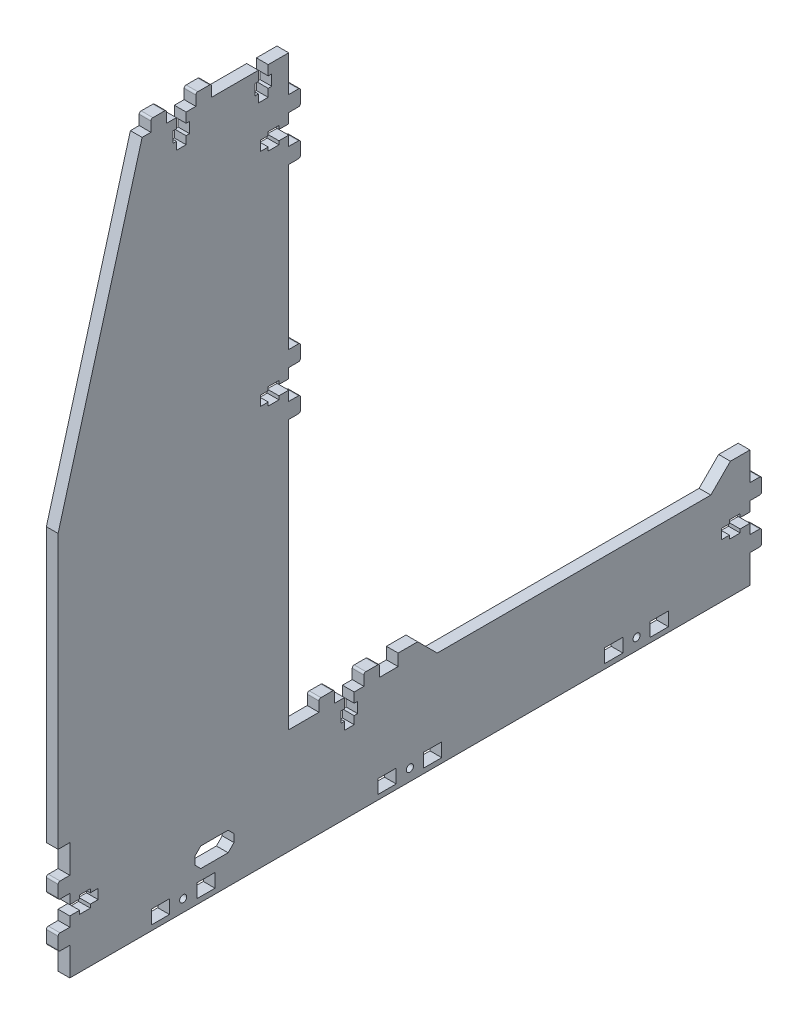
SolidWorks part; units mm, degrees
ref_plane "Plan de face" through (0, 0, 0) normal (0, 0, 1) x (1, 0, 0)
ref_plane "Plan de dessus" through (0, 0, 0) normal (0, 1, 0) x (1, 0, 0)
ref_plane "Plan de droite" through (0, 0, 0) normal (1, 0, 0) x (0, 0, -1)
sketch "Esquisse2" plane through (0, 0, 0) normal (1, 0, 0) x (0, 0, -1)
  line L0 (-180, 200) -> (-180, 60)
  line L1 (-180, 200) -> (-137, 354)
  line L2 (-137, 354) -> (-62, 354)
  line L3 (-62, 354) -> (-62, 54)
  line L4 (-62, 54) -> (-6, 54)
  line L5 (-6, 54) -> (-6, 60)
  line L6 (-6, 60) -> (4, 60)
  line L7 (4, 60) -> (14, 50)
  line L8 (14, 50) -> (154, 50)
  line L9 (154, 50) -> (164, 60)
  line L10 (164, 60) -> (174, 60)
  line L11 (174, 60) -> (174, 0)
  line L12 (174, 0) -> (-174, 0)
  line L13 (4, 60) -> (119.7586, 60) construction
  line L14 (-180, 60) -> (-174, 60)
  line L15 (-62, 204) -> (0, 204) construction
  line L16 (-174, 60) -> (-174, 0)
  line L17 (0, 0) -> (0, 204) construction
  line L18 (-174, 6) -> (174, 6) construction
  point P2 (0, 0)
  point P18 (-62, 204)
  line B0 (-132.3, 9.6336) -> (-123, 9.6336)
  line B1 (-132.3, 9.6336) -> (-132.3, 2.6336)
  line B2 (-132.3, 2.6336) -> (-123, 2.6336)
  line B3 (-123, 9.6336) -> (-123, 2.6336)
  line B4 (-109, 9.6336) -> (-109, 2.6336)
  line B5 (-99.7, 2.6336) -> (-109, 2.6336)
  line B6 (-99.7, 9.6336) -> (-99.7, 2.6336)
  line B7 (-99.7, 9.6336) -> (-109, 9.6336)
  circle B8 centre (-116, 6.1336) radius 1.8
  line B9 (-16.3, 9.5) -> (-7, 9.5)
  line B10 (-16.3, 9.5) -> (-16.3, 2.5)
  line B11 (-16.3, 2.5) -> (-7, 2.5)
  line B12 (-7, 9.5) -> (-7, 2.5)
  line B13 (7, 9.5) -> (7, 2.5)
  line B14 (16.3, 2.5) -> (7, 2.5)
  line B15 (16.3, 9.5) -> (16.3, 2.5)
  line B16 (16.3, 9.5) -> (7, 9.5)
  circle B17 centre (0, 6) radius 1.8
  line B18 (99.7, 9.5) -> (109, 9.5)
  line B19 (99.7, 9.5) -> (99.7, 2.5)
  line B20 (99.7, 2.5) -> (109, 2.5)
  line B21 (109, 9.5) -> (109, 2.5)
  line B22 (123, 9.5) -> (123, 2.5)
  line B23 (132.3, 2.5) -> (123, 2.5)
  line B24 (132.3, 9.5) -> (132.3, 2.5)
  line B25 (132.3, 9.5) -> (123, 9.5)
  circle B26 centre (116, 6) radius 1.8
  dimension "D1" = 348
  dimension "D2" = 354
  dimension "D3" = 75
  dimension "D4" = 62
  dimension "D5" = 56
  dimension "D6" = 6
  dimension "D7" = 10
  dimension "D8" = 10
  dimension "D9" = 118
  dimension "D10" = 45
  dimension "D11" = 10
  dimension "D12" = 60
  dimension "D14" = 6
  dimension "D15" = 58
  dimension "s" = 200
  dimension "D16" = 58
sketch_block_instance "attache_femelle-1"
sketch_block "attache_femelle" parameters "D1"=3.6, "D2"=9.3, "D3"=7, "D4"=7
sketch_block_instance "attache_femelle-2"
sketch_block_instance "attache_femelle-5"
extrude "Boss.-Extru.1" add sketch "Esquisse2" along normal mid plane 6
sketch "Esquisse4" plane through (3, 0, 0) normal (1, 0, 0) x (0, 0, -1)
  line L0 (174, 30) -> (-174, 30) construction
  line L1 (-62, 54) -> (-62, 360) construction
  line L2 (-6, 54) -> (-56, 54) construction
  line L3 (-174, 0) -> (174, 0) construction
  line L8 (174, 0) -> (174, 60) construction
  line L10 (-62, 54) -> (-62, 354) construction
  line L11 (-6, 54) -> (-62, 54) construction
  line L12 (-174, 60) -> (-174, 0) construction
  line L13 (-62, 354) -> (-137, 354) construction
  line B0 (-174, 14.5) -> (-179, 14.5)
  line B1 (-180, 15.5) -> (-180, 21.5)
  line B2 (-179, 22.5) -> (-174, 22.5)
  line B3 (-174, 22.5) -> (-174, 27.5)
  line B4 (-174, 27.5) -> (-169, 27.5)
  line B5 (-169, 27.5) -> (-169, 25.7)
  line B6 (-169, 25.7) -> (-163.5, 25.7)
  line B7 (-163.5, 25.7) -> (-163.5, 27.5)
  line B8 (-163.5, 27.5) -> (-159.5, 27.5)
  line B9 (-159.5, 27.5) -> (-159.5, 32.5)
  line B10 (-159.5, 30) -> (-174, 30) construction
  line B11 (-174, 45.5) -> (-174, 37.5)
  line B12 (-174, 22.5) -> (-174, 14.5)
  line B13 (-163.5, 32.5) -> (-159.5, 32.5)
  line B14 (-163.5, 34.3) -> (-163.5, 32.5)
  line B15 (-169, 34.3) -> (-163.5, 34.3)
  line B16 (-169, 32.5) -> (-169, 34.3)
  line B17 (-174, 32.5) -> (-169, 32.5)
  line B18 (-174, 37.5) -> (-174, 32.5)
  line B19 (-179, 37.5) -> (-174, 37.5)
  line B20 (-180, 44.5) -> (-180, 38.5)
  line B21 (-174, 45.5) -> (-179, 45.5)
  line B22 (-174, 27.5) -> (-174, 32.5)
  arc B23 (-180, 21.5) -> (-179, 22.5) centre (-179, 21.5) cw
  arc B24 (-179, 14.5) -> (-180, 15.5) centre (-179, 15.5) cw
  arc B25 (-179, 45.5) -> (-180, 44.5) centre (-179, 44.5) ccw
  arc B26 (-180, 38.5) -> (-179, 37.5) centre (-179, 38.5) ccw
  line B27 (174, 45.5) -> (179, 45.5)
  line B28 (180, 44.5) -> (180, 38.5)
  line B29 (179, 37.5) -> (174, 37.5)
  line B30 (174, 37.5) -> (174, 32.5)
  line B31 (174, 32.5) -> (169, 32.5)
  line B32 (169, 32.5) -> (169, 34.3)
  line B33 (169, 34.3) -> (163.5, 34.3)
  line B34 (163.5, 34.3) -> (163.5, 32.5)
  line B35 (163.5, 32.5) -> (159.5, 32.5)
  line B36 (159.5, 32.5) -> (159.5, 27.5)
  line B37 (159.5, 30) -> (174, 30) construction
  line B38 (174, 14.5) -> (174, 22.5)
  line B39 (174, 37.5) -> (174, 45.5)
  line B40 (163.5, 27.5) -> (159.5, 27.5)
  line B41 (163.5, 25.7) -> (163.5, 27.5)
  line B42 (169, 25.7) -> (163.5, 25.7)
  line B43 (169, 27.5) -> (169, 25.7)
  line B44 (174, 27.5) -> (169, 27.5)
  line B45 (174, 22.5) -> (174, 27.5)
  line B46 (179, 22.5) -> (174, 22.5)
  line B47 (180, 15.5) -> (180, 21.5)
  line B48 (174, 14.5) -> (179, 14.5)
  line B49 (174, 32.5) -> (174, 27.5)
  arc B50 (180, 38.5) -> (179, 37.5) centre (179, 38.5) cw
  arc B51 (179, 45.5) -> (180, 44.5) centre (179, 44.5) cw
  arc B52 (179, 14.5) -> (180, 15.5) centre (179, 15.5) ccw
  arc B53 (180, 21.5) -> (179, 22.5) centre (179, 21.5) ccw
  line B54 (-46.5, 54) -> (-46.5, 59)
  line B55 (-45.5, 60) -> (-39.5, 60)
  line B56 (-38.5, 59) -> (-38.5, 54)
  line B57 (-38.5, 54) -> (-33.5, 54)
  line B58 (-33.5, 54) -> (-33.5, 49)
  line B59 (-33.5, 49) -> (-35.3, 49)
  line B60 (-35.3, 49) -> (-35.3, 43.5)
  line B61 (-35.3, 43.5) -> (-33.5, 43.5)
  line B62 (-33.5, 43.5) -> (-33.5, 39.5)
  line B63 (-33.5, 39.5) -> (-28.5, 39.5)
  line B64 (-31, 39.5) -> (-31, 54) construction
  line B65 (-15.5, 54) -> (-23.5, 54)
  line B66 (-38.5, 54) -> (-46.5, 54)
  line B67 (-28.5, 43.5) -> (-28.5, 39.5)
  line B68 (-26.7, 43.5) -> (-28.5, 43.5)
  line B69 (-26.7, 49) -> (-26.7, 43.5)
  line B70 (-28.5, 49) -> (-26.7, 49)
  line B71 (-28.5, 54) -> (-28.5, 49)
  line B72 (-23.5, 54) -> (-28.5, 54)
  line B73 (-23.5, 59) -> (-23.5, 54)
  line B74 (-16.5, 60) -> (-22.5, 60)
  line B75 (-15.5, 54) -> (-15.5, 59)
  line B76 (-33.5, 54) -> (-28.5, 54)
  arc B77 (-39.5, 60) -> (-38.5, 59) centre (-39.5, 59) cw
  arc B78 (-46.5, 59) -> (-45.5, 60) centre (-45.5, 59) cw
  arc B79 (-15.5, 59) -> (-16.5, 60) centre (-16.5, 59) ccw
  arc B80 (-22.5, 60) -> (-23.5, 59) centre (-22.5, 59) ccw
  line B81 (-62, 222.5) -> (-57, 222.5)
  line B82 (-56, 221.5) -> (-56, 215.5)
  line B83 (-57, 214.5) -> (-62, 214.5)
  line B84 (-62, 214.5) -> (-62, 209.5)
  line B85 (-62, 209.5) -> (-67, 209.5)
  line B86 (-67, 209.5) -> (-67, 211.3)
  line B87 (-67, 211.3) -> (-72.5, 211.3)
  line B88 (-72.5, 211.3) -> (-72.5, 209.5)
  line B89 (-72.5, 209.5) -> (-76.5, 209.5)
  line B90 (-76.5, 209.5) -> (-76.5, 204.5)
  line B91 (-76.5, 207) -> (-62, 207) construction
  line B92 (-62, 191.5) -> (-62, 199.5)
  line B93 (-62, 214.5) -> (-62, 222.5)
  line B94 (-72.5, 204.5) -> (-76.5, 204.5)
  line B95 (-72.5, 202.7) -> (-72.5, 204.5)
  line B96 (-67, 202.7) -> (-72.5, 202.7)
  line B97 (-67, 204.5) -> (-67, 202.7)
  line B98 (-62, 204.5) -> (-67, 204.5)
  line B99 (-62, 199.5) -> (-62, 204.5)
  line B100 (-57, 199.5) -> (-62, 199.5)
  line B101 (-56, 192.5) -> (-56, 198.5)
  line B102 (-62, 191.5) -> (-57, 191.5)
  line B103 (-62, 209.5) -> (-62, 204.5)
  arc B104 (-56, 215.5) -> (-57, 214.5) centre (-57, 215.5) cw
  arc B105 (-57, 222.5) -> (-56, 221.5) centre (-57, 221.5) cw
  arc B106 (-57, 191.5) -> (-56, 192.5) centre (-57, 192.5) ccw
  arc B107 (-56, 198.5) -> (-57, 199.5) centre (-57, 198.5) ccw
  line B108 (-62, 335.5) -> (-57, 335.5)
  line B109 (-56, 334.5) -> (-56, 328.5)
  line B110 (-57, 327.5) -> (-62, 327.5)
  line B111 (-62, 327.5) -> (-62, 322.5)
  line B112 (-62, 322.5) -> (-67, 322.5)
  line B113 (-67, 322.5) -> (-67, 324.3)
  line B114 (-67, 324.3) -> (-72.5, 324.3)
  line B115 (-72.5, 324.3) -> (-72.5, 322.5)
  line B116 (-72.5, 322.5) -> (-76.5, 322.5)
  line B117 (-76.5, 322.5) -> (-76.5, 317.5)
  line B118 (-76.5, 320) -> (-62, 320) construction
  line B119 (-62, 304.5) -> (-62, 312.5)
  line B120 (-62, 327.5) -> (-62, 335.5)
  line B121 (-72.5, 317.5) -> (-76.5, 317.5)
  line B122 (-72.5, 315.7) -> (-72.5, 317.5)
  line B123 (-67, 315.7) -> (-72.5, 315.7)
  line B124 (-67, 317.5) -> (-67, 315.7)
  line B125 (-62, 317.5) -> (-67, 317.5)
  line B126 (-62, 312.5) -> (-62, 317.5)
  line B127 (-57, 312.5) -> (-62, 312.5)
  line B128 (-56, 305.5) -> (-56, 311.5)
  line B129 (-62, 304.5) -> (-57, 304.5)
  line B130 (-62, 322.5) -> (-62, 317.5)
  arc B131 (-56, 328.5) -> (-57, 327.5) centre (-57, 328.5) cw
  arc B132 (-57, 335.5) -> (-56, 334.5) centre (-57, 334.5) cw
  arc B133 (-57, 304.5) -> (-56, 305.5) centre (-57, 305.5) ccw
  arc B134 (-56, 311.5) -> (-57, 312.5) centre (-57, 311.5) ccw
  line B135 (-90.5, 354) -> (-90.5, 359)
  line B136 (-89.5, 360) -> (-83.5, 360)
  line B137 (-82.5, 359) -> (-82.5, 354)
  line B138 (-82.5, 354) -> (-77.5, 354)
  line B139 (-77.5, 354) -> (-77.5, 349)
  line B140 (-77.5, 349) -> (-79.3, 349)
  line B141 (-79.3, 349) -> (-79.3, 343.5)
  line B142 (-79.3, 343.5) -> (-77.5, 343.5)
  line B143 (-77.5, 343.5) -> (-77.5, 339.5)
  line B144 (-77.5, 339.5) -> (-72.5, 339.5)
  line B145 (-75, 339.5) -> (-75, 354) construction
  line B146 (-59.5, 354) -> (-67.5, 354)
  line B147 (-82.5, 354) -> (-90.5, 354)
  line B148 (-72.5, 343.5) -> (-72.5, 339.5)
  line B149 (-70.7, 343.5) -> (-72.5, 343.5)
  line B150 (-70.7, 349) -> (-70.7, 343.5)
  line B151 (-72.5, 349) -> (-70.7, 349)
  line B152 (-72.5, 354) -> (-72.5, 349)
  line B153 (-67.5, 354) -> (-72.5, 354)
  line B154 (-67.5, 359) -> (-67.5, 354)
  line B155 (-60.5, 360) -> (-66.5, 360)
  line B156 (-59.5, 354) -> (-59.5, 359)
  line B157 (-77.5, 354) -> (-72.5, 354)
  arc B158 (-83.5, 360) -> (-82.5, 359) centre (-83.5, 359) cw
  arc B159 (-90.5, 359) -> (-89.5, 360) centre (-89.5, 359) cw
  arc B160 (-59.5, 359) -> (-60.5, 360) centre (-60.5, 359) ccw
  arc B161 (-66.5, 360) -> (-67.5, 359) centre (-66.5, 359) ccw
  line B162 (-132.5, 354) -> (-132.5, 359)
  line B163 (-131.5, 360) -> (-125.5, 360)
  line B164 (-124.5, 359) -> (-124.5, 354)
  line B165 (-124.5, 354) -> (-119.5, 354)
  line B166 (-119.5, 354) -> (-119.5, 349)
  line B167 (-119.5, 349) -> (-121.3, 349)
  line B168 (-121.3, 349) -> (-121.3, 343.5)
  line B169 (-121.3, 343.5) -> (-119.5, 343.5)
  line B170 (-119.5, 343.5) -> (-119.5, 339.5)
  line B171 (-119.5, 339.5) -> (-114.5, 339.5)
  line B172 (-117, 339.5) -> (-117, 354) construction
  line B173 (-101.5, 354) -> (-109.5, 354)
  line B174 (-124.5, 354) -> (-132.5, 354)
  line B175 (-114.5, 343.5) -> (-114.5, 339.5)
  line B176 (-112.7, 343.5) -> (-114.5, 343.5)
  line B177 (-112.7, 349) -> (-112.7, 343.5)
  line B178 (-114.5, 349) -> (-112.7, 349)
  line B179 (-114.5, 354) -> (-114.5, 349)
  line B180 (-109.5, 354) -> (-114.5, 354)
  line B181 (-109.5, 359) -> (-109.5, 354)
  line B182 (-102.5, 360) -> (-108.5, 360)
  line B183 (-101.5, 354) -> (-101.5, 359)
  line B184 (-119.5, 354) -> (-114.5, 354)
  arc B185 (-125.5, 360) -> (-124.5, 359) centre (-125.5, 359) cw
  arc B186 (-132.5, 359) -> (-131.5, 360) centre (-131.5, 359) cw
  arc B187 (-101.5, 359) -> (-102.5, 360) centre (-102.5, 359) ccw
  arc B188 (-108.5, 360) -> (-109.5, 359) centre (-108.5, 359) ccw
  line B189 (-110, 22) -> (-107, 25)
  line B190 (-107, 15) -> (-93, 15)
  line B191 (-110, 18) -> (-110, 22)
  line B192 (-107, 25) -> (-93, 25)
  line B193 (-90, 18) -> (-90, 22)
  line B194 (-110, 15) -> (-90, 25) construction
  line B195 (-110, 25) -> (-90, 15) construction
  line B196 (-93, 25) -> (-90, 22)
  line B197 (-93, 15) -> (-90, 18)
  line B198 (-110, 18) -> (-107, 15)
  dimension "D1" = 20
  dimension "D2" = 13
  dimension "D3" = 34
  dimension "D4" = 6
  dimension "D5" = 6
  dimension "D6" = 100
  dimension "D7" = 20
sketch_block_instance "attache_male-1"
sketch_block "attache_male" parameters "D7"=1, "D1"=5, "D2"=5, "D3"=5.5, "D4"=1.8, "D5"=4, "D6"=2.5
sketch_block_instance "attache_male-2"
sketch_block_instance "attache_male-3"
sketch_block_instance "attache_male-4"
sketch_block_instance "attache_male-5"
sketch_block_instance "attache_male-6"
sketch_block_instance "attache_male-7"
sketch_block_instance "cable_hole-1"
sketch_block "cable_hole" parameters "D1"=20, "D2"=10
extrude "Boss.-Extru.2" add sketch "Esquisse4" against normal blind 6 contours B186 B162 B164 B185 B163 | B182 B188 B181 B183 B187 | B132 B108 B110 B131 B109 | B128 B134 B127 B129 B133 | B105 B81 B83 B104 B82 | B101 B107 B100 B102 B106 | B20 B26 B19 B21 B25 | B24 B0 B2 B23 B1 | B78 B54 B56 B77 B55 | B74 B80 B73 B75 B79 | B51 B27 B29 B50 B28 | B47 B53 B46 B48 B52 region at (3, 41.5, 176.9749) region at (3, 18.5, 176.9749) region at (3, 18.5, -176.9749) region at (3, 41.5, -176.9749) region at (3, 56.9749, 19.5) region at (3, 56.9749, 42.5) region at (3, 195.5, 59.0251) region at (3, 218.5, 59.0251) region at (3, 308.5, 59.0251) region at (3, 331.5, 59.0251) region at (3, 356.9749, 105.5) region at (3, 356.9749, 128.5)
extrude "Enlèv. mat.-Extru.1" cut sketch "Esquisse4<3>" against normal blind 6 contours B179 B166 B167 B168 B169 B170 B171 B175 B176 B177 B178 | B152 B139 B140 B141 B142 B143 B144 B148 B149 B150 B151 | B125 B112 B113 B114 B115 B116 B117 B121 B122 B123 B124 | B98 B85 B86 B87 B88 B89 B90 B94 B95 B96 B97 | B71 B58 B59 B60 B61 B62 B63 B67 B68 B69 B70 | B22 B4 B5 B6 B7 B8 B9 | B9 B13 B14 B15 B16 B17 | B36 B49 B31 B32 B33 B34 B35 | B36 B40 B41 B42 B43 B44 | B191 B198 B190 B197 B193 B196 B192 B189 region at (3, 30, 166.6427) region at (3, 30, -166.6427) region at (3, 46.6427, 31) region at (3, 207, 69.3573) region at (3, 320, 69.3573) region at (3, 346.6427, 75) region at (3, 346.6427, 117) region at (3, 20, 100)
sketch "Esquisse4<3>" plane through (3, 0, 0) normal (1, 0, 0) x (0, 0, -1) same geometry as "Esquisse4"
equation "\"L\"= \"L@Prusa i4.2.sldasm\""
equation "\"H\"= \"H@Prusa i4.2.sldasm\""
equation "\"D1@Esquisse2\"=\"L\""
equation "\"D2@Esquisse2\"=\"H\"-6"
equation "\"s\"=175"
equation "\"D16@Esquisse2\"=\"L\"/6"
equation "\"D15@Esquisse2\"=\"L\"/6"
